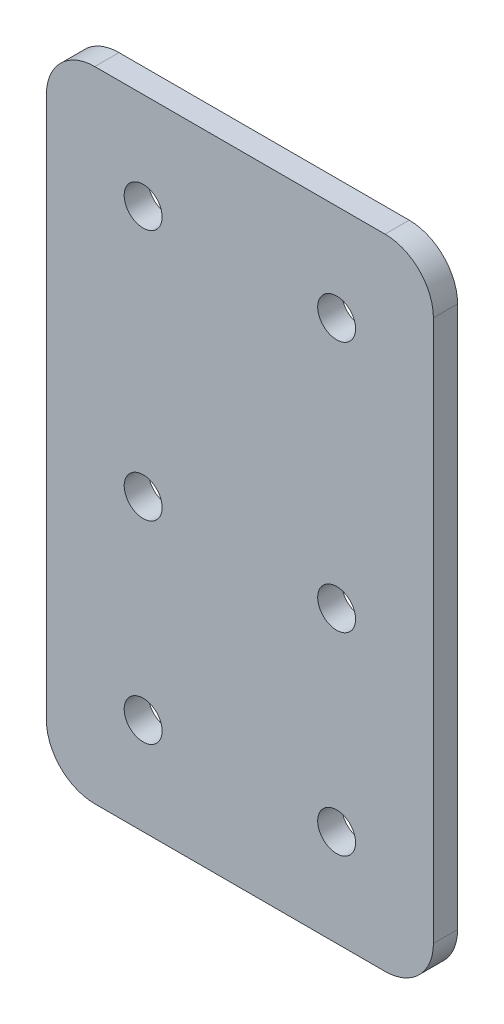
SolidWorks part; units mm, degrees
material "6061-T6 (SS)"
ref_plane "Front Plane" through (0, 0, 0) normal (0, 0, 1) x (1, 0, 0)
ref_plane "Top Plane" through (0, 0, 0) normal (0, 1, 0) x (1, 0, 0)
ref_plane "Right Plane" through (0, 0, 0) normal (1, 0, 0) x (0, 0, -1)
sketch "Sketch2" plane through (0, 0, 0) normal (0, 0, 1) x (1, 0, 0)
  line L1 (0, 0) -> (50.8, 0)
  line L2 (0, 0) -> (0, 83.82)
  line L3 (0, 83.82) -> (50.8, 83.82)
  line L6 (50.8, 83.82) -> (50.8, 0)
  dimension "D1" = 50.8
  dimension "D2" = 83.82
extrude "Boss-Extrude1" add sketch "Sketch2" against normal blind 3.175
sketch "Sketch3" plane through (0, 0, 0) normal (0, 0, 1) x (1, 0, 0)
  line L0 (50.8, 83.82) -> (0, 83.82) construction
  line L1 (0, 83.82) -> (0, 0) construction
  circle A0 centre (12.7, 71.12) radius 2.4892
  circle A17 centre (38.1, 71.12) radius 2.4892
  circle A24 centre (12.7, 38.1) radius 2.4892
  circle A25 centre (12.7, 12.7) radius 2.4892
  circle A26 centre (12.7, -12.7) radius 2.4892
  circle A27 centre (12.7, -38.1) radius 2.4892
  circle A28 centre (12.7, -63.5) radius 2.4892
  circle A33 centre (38.1, 12.7) radius 2.4892
  circle A34 centre (38.1, -12.7) radius 2.4892
  circle A35 centre (38.1, -38.1) radius 2.4892
  circle A36 centre (38.1, -63.5) radius 2.4892
  circle A41 centre (38.1, 38.1) radius 2.4892
  dimension "D1" = 4.9784
  dimension "D6" = 4.9784
  dimension "D2" = 12.7
  dimension "D3" = 12.7
  dimension "D7" = 12.7
  dimension "D8" = 33.02
  dimension "D4" = 1
  dimension "D5" = 2
  dimension "D9" = 5
  dimension "D10" = 2
extrude "Cut-Extrude1" cut sketch "Sketch3" against normal through all
fillet "Fillet1" radius 6.35 4 edges at (0, 0, -1.5875) (0, 83.82, -1.5875) (50.8, 0, -1.5875) (50.8, 83.82, -1.5875)
